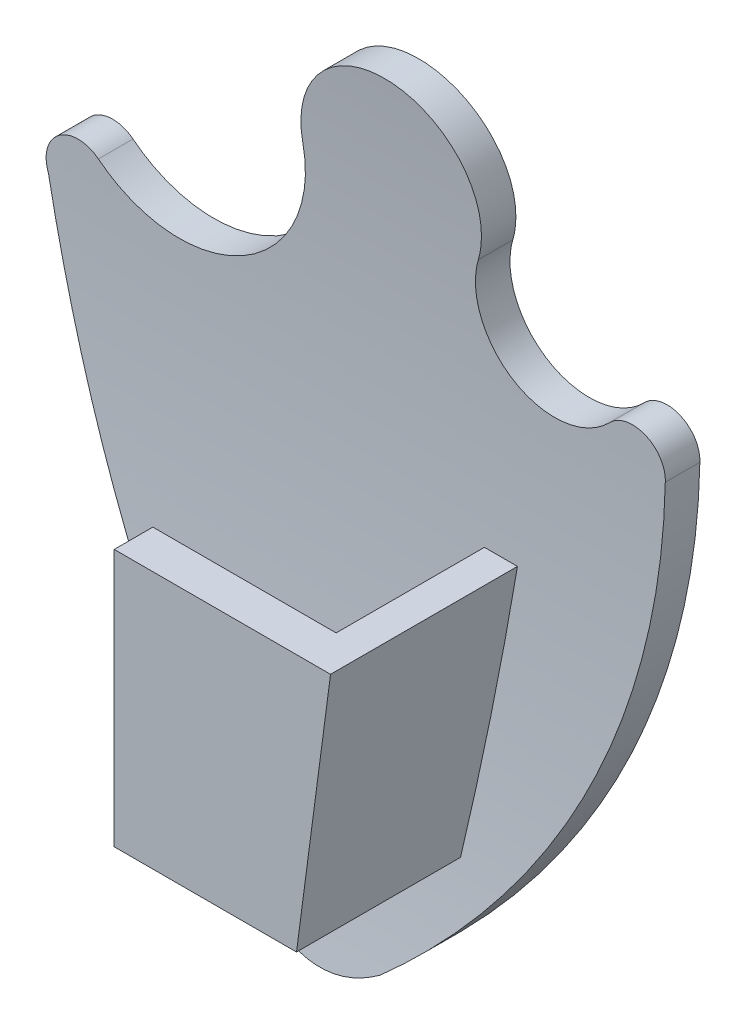
SolidWorks part; units mm, degrees
ref_plane "Front Plane" through (0, 0, 0) normal (0, 0, 1) x (1, 0, 0)
ref_plane "Top Plane" through (0, 0, 0) normal (0, 1, 0) x (1, 0, 0)
ref_plane "Right Plane" through (0, 0, 0) normal (1, 0, 0) x (0, 0, -1)
sketch "Sketch1" plane through (0, 0, 0) normal (0, 0, 1) x (1, 0, 0)
  line L1 (-25, 45) -> (25, 45)
  line L2 (-25, 45) -> (-25, -45)
  line L3 (-25, -45) -> (25, -45)
  line L4 (25, 45) -> (25, -45)
  line L5 (-25, 45) -> (25, -45) construction
  line L6 (-25, -45) -> (25, 45) construction
  point P0 (0, 0)
  dimension "D1" = 90
  dimension "D2" = 50
extrude "Boss-Extrude1" add sketch "Sketch1" along normal blind 20
sketch "Sketch2" plane through (0, 0, 0) normal (1, 0, 0) x (0, 0, -1)
  line L0 (-20, 45) -> (0, 45) construction
  line L1 (-20, -45) -> (0, -45) construction
  line L3 (0, 45) -> (-20, 45)
  line L4 (0, 45) -> (0, -45)
  line L5 (0, -45) -> (-20, -45)
  line L6 (-20, 45) -> (-20, -45)
  spline S0 degree 2 poles (-20, 45) (-10.5799, 0.3961) (-20, -45) knots 0 0 0 1 1 1
  spline S1 degree 2 poles (-17.5, 45) (-7.7076, 0.4027) (-17.5, -45) knots 0 0 0 1 1 1
  dimension "D1" = 2.5
  dimension "D2" = 2.5
extrude "Cut-Extrude1" cut sketch "Sketch2" against normal through all both and the other way through all contours L3 S1 L5 L4 | S0 L6 region at (0, -0.0185, 7.1928) region at (0, 0.0792, 18.116)
sketch "Sketch3" plane through (0, 0, 0) normal (0, 0, 1) x (1, 0, 0)
  line L0 (0, -39.5048) -> (0, 39.5048) construction
  line L14 (26.2479, 47.9226) -> (-27.147, 47.9226)
  line L15 (26.2479, 47.9226) -> (26.2479, -49.5468)
  line L16 (26.2479, -49.5468) -> (-27.147, -49.5468)
  line L17 (-27.147, 47.9226) -> (-27.147, -49.5468)
  circle A0 centre (0, -36.1825) radius 5
  circle A3 centre (-14.6622, 9.7375) radius 10
  circle A4 centre (2.14, 12.3229) radius 7
  circle A5 centre (14.4954, 8.28) radius 6
  circle A6 centre (-22.5, 0) radius 2.5
  circle A7 centre (20.5929, 2.358) radius 2.5
  spline S0 degree 2 poles (4.4079, -38.5426) (22.4074, -22.8392) (23.0929, 2.358) knots 0 0 0 1 1 1
  spline S1 degree 2 poles (-4.4079, -38.5426) (-20.7008, -23.0083) (-25, 0) knots 0 0 0 1 1 1
  point P8 (0, 0)
  dimension "D1" = 10
  dimension "D2" = 14
  dimension "D3" = 12
  dimension "D4" = 20
  dimension "D5" = 5
  dimension "D6" = 5
extrude "Cut-Extrude3" cut sketch "Sketch3" against normal through all both and the other way through all contours L14 L17 L16 L15 A0 S1 A6 A3 A4 A5 A7 S0 | A3 | A5 region at (25.1365, -0.8121, 0) region at (14.4954, 8.28, 0) region at (-14.6622, 9.7375, 0)
sketch "Sketch4" plane through (0, 0, 0) normal (0, 0, 1) x (1, 0, 0)
  line L0 (4.4079, -38.5426) -> (7.8343, -41.9689)
  line L1 (7.8343, -41.9689) -> (-6.0066, -43.2891)
  line L2 (-6.0066, -43.2891) -> (-4.4079, -38.5426)
  spline S0 degree 2 poles (-4.4079, -38.5426) (0, -41.606) (4.4079, -38.5426) knots 0 0 0 1 1 1
extrude "Cut-Extrude4" cut sketch "Sketch4" against normal through all both and the other way through all
sketch "Sketch5" plane through (0, 0, 0) normal (0, 0, 1) x (1, 0, 0)
  line L0 (9.2307, -8.9911) -> (6.5866, -28.9911)
  line L1 (6.5866, -28.9911) -> (9.1531, -28.9911)
  line L2 (9.1531, -28.9911) -> (11.7973, -8.9911)
  line L3 (11.7973, -8.9911) -> (9.2307, -8.9911)
  dimension "D1" = 20
extrude "Boss-Extrude2" add sketch "Sketch5" along normal blind 15 from offset 15
sketch "Sketch6" plane through (0, 0, 0) normal (1, 0, 0) x (0, 0, -1)
  line L0 (-30, -28.9911) -> (-17.2604, -28.9911) construction
  line L1 (-30, -8.9911) -> (-27, -8.9911)
  line L2 (-30, -8.9911) -> (-30, -28.9911)
  line L3 (-30, -28.9911) -> (-27, -28.9911)
  line L4 (-27, -8.9911) -> (-27, -28.9911)
  dimension "D1" = 3
extrude "Boss-Extrude3" add sketch "Sketch6" against normal blind 15 from offset 10
sketch "Sketch7" plane through (0, 0, 0) normal (0, 0, 1) x (1, 0, 0)
  line L0 (9.1531, -28.9911) -> (10.3029, -20.2943)
  line L1 (9.1531, -28.9911) -> (11.7973, -8.9911) construction
  line L2 (10.3029, -20.2943) -> (11.652, -29.3215)
  line L3 (11.652, -29.3215) -> (9.1531, -28.9911)
extrude "Cut-Extrude5" cut sketch "Sketch7" along normal blind 20 from offset 20
